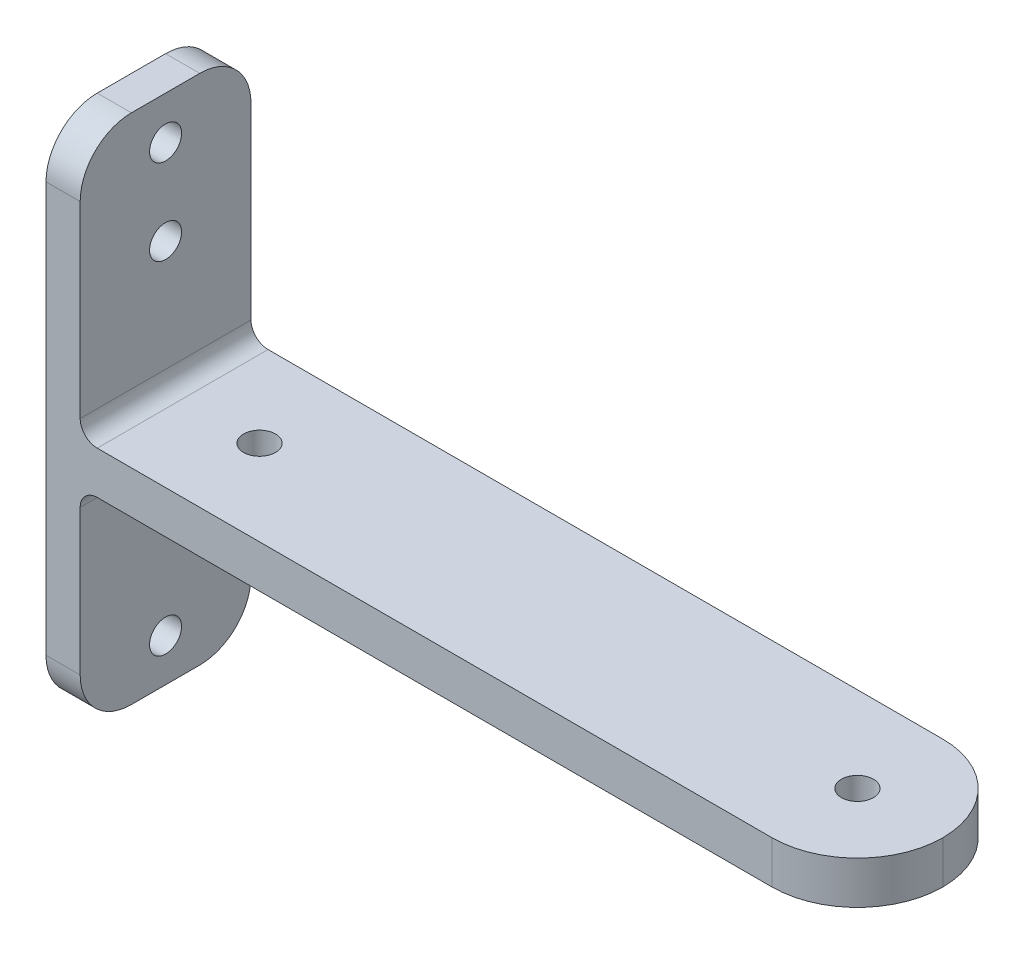
SolidWorks part; units mm, degrees
material "Brass"
ref_plane "Front Plane" through (0, 0, 0) normal (0, 0, 1) x (1, 0, 0)
ref_plane "Top Plane" through (0, 0, 0) normal (0, 1, 0) x (1, 0, 0)
ref_plane "Right Plane" through (0, 0, 0) normal (1, 0, 0) x (0, 0, -1)
sketch "Sketch1" plane through (0, 0, 0) normal (0, 1, 0) x (1, 0, 0)
  line L1 (-60.325, 12.7) -> (60.325, 12.7)
  line L2 (-60.325, 12.7) -> (-60.325, -12.7)
  line L3 (-60.325, -12.7) -> (60.325, -12.7)
  line L4 (60.325, 12.7) -> (60.325, -12.7)
  line L5 (-60.325, 12.7) -> (60.325, -12.7) construction
  line L6 (-60.325, -12.7) -> (60.325, 12.7) construction
  circle A0 centre (47.625, 0) radius 2.3812
  point P0 (0, 0)
  dimension "D3" = 4.7625
  dimension "D1" = 120.65
  dimension "D2" = 25.4
  dimension "D4" = 107.95
extrude "Boss-Extrude1" add sketch "Sketch1" along normal blind 6.35
sketch "Sketch2" plane through (0, 6.35, 0) normal (0, 1, 0) x (1, 0, 0)
  line L0 (-60.325, 12.7) -> (-60.325, -12.7) construction
  circle A0 centre (-41.275, 0) radius 2.3812
  point P4 (0, 0)
  dimension "D1" = 4.7625
  dimension "D2" = 19.05
extrude "Cut-Extrude1" cut sketch "Sketch2" against normal blind 6.35
sketch "Sketch3" plane through (0, 6.35, 0) normal (0, 1, 0) x (1, 0, 0)
  line L0 (-60.325, -12.7) -> (60.325, -12.7) construction
  line L1 (-60.325, 12.7) -> (-55.245, 12.7)
  line L2 (-60.325, 12.7) -> (-60.325, -12.7)
  line L3 (-60.325, -12.7) -> (-55.245, -12.7)
  line L4 (-55.245, 12.7) -> (-55.245, -12.7)
  dimension "D1" = 5.08
extrude "Boss-Extrude2" add sketch "Sketch3" along normal blind 38.1 and the other way blind 38.1
sketch "Sketch4" plane through (-60.325, 0, 0) normal (-1, 0, 0) x (0, 0, 1)
  circle A0 centre (0, 0) radius 25.4 construction
  circle A1 centre (0, 25.4) radius 2.3813
  circle A2 centre (0, -25.4) radius 2.3813
  circle A3 centre (0, 0) radius 38.1 construction
  circle A4 centre (0, 38.1) radius 2.3812
  dimension "D1" = 50.8
  dimension "D2" = 4.7625
  dimension "D3" = 4.7625
  dimension "D4" = 76.2
  dimension "D5" = 4.7625
extrude "Cut-Extrude2" cut sketch "Sketch4" against normal through all
fillet "Fillet1" radius 2.54 2 edges at (-55.245, 0, 0) (-55.245, 6.35, 0)
fillet "Fillet2" radius 7.62 4 edges at (-57.785, -31.75, 12.7) (-57.785, -31.75, -12.7) (-57.785, 44.45, 12.7) (-57.785, 44.45, -12.7)
fillet "Fillet3" radius 12.7 2 edges at (60.325, 3.175, 12.7) (60.325, 3.175, -12.7)
